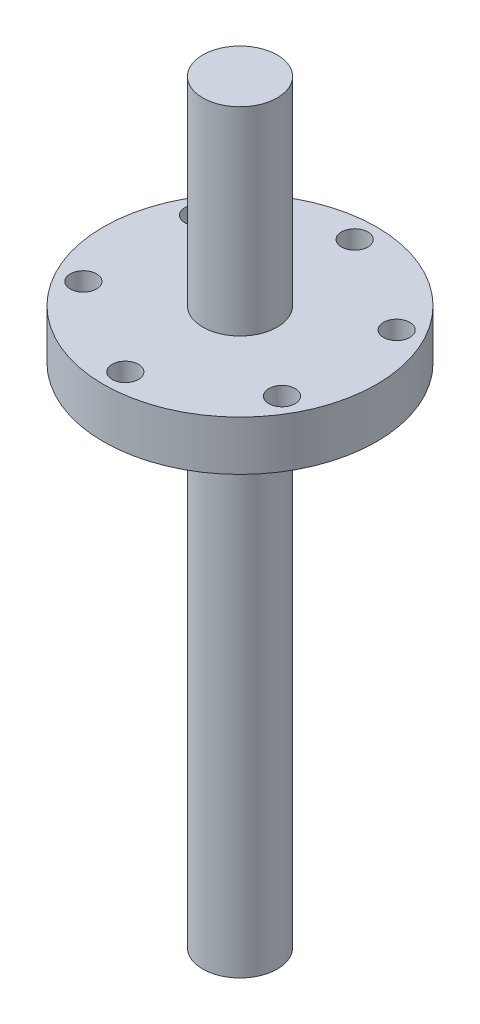
SolidWorks part; units mm, degrees
ref_plane "Front Plane" through (0, 0, 0) normal (0, 0, 1) x (1, 0, 0)
ref_plane "Top Plane" through (0, 0, 0) normal (0, 1, 0) x (1, 0, 0)
ref_plane "Right Plane" through (0, 0, 0) normal (1, 0, 0) x (0, 0, -1)
sketch "Sketch1" plane through (0, 0, 0) normal (0, 1, 0) x (1, 0, 0)
  circle A0 centre (0, 0) radius 34.925
  dimension "D1" = 69.85
extrude "Extrude1" add sketch "Sketch1" along normal blind 12.7
sketch "Sketch2" plane through (0, 0, 0) normal (0, 1, 0) x (1, 0, 0)
  circle A0 centre (0, 0) radius 17.399
  dimension "D1" = 34.798
extrude "Cut-Extrude1" [suppressed] cut sketch "Sketch2" along normal through all
sketch "Sketch3" plane through (0, 0, 0) normal (0, 1, 0) x (1, 0, 0)
  circle A0 centre (0, 29.337) radius 3.3655
  dimension "D1" = 6.731
  dimension "D2" = 29.337
extrude "Cut-Extrude2" cut sketch "Sketch3" along normal blind 12.7
ref_axis "Axis1" through (0, 35.8582, 0) along (0, -1, 0)
pattern_circular "CirPattern1" count 6 over 360 about axis through (0, 35.8582, 0) along (0, -1, 0) of "Cut-Extrude2"
sketch "Sketch4" plane through (0, 0, 0) normal (0, 1, 0) x (1, 0, 0)
  line L0 (0, 0) -> (0, 16.8619)
sketch "Sketch5" plane through (0, 0, 0) normal (0, 1, 0) x (1, 0, 0)
  circle A0 centre (0, 0) radius 9.525
  dimension "D1" = 19.05
extrude "Extrude2" add sketch "Sketch5" against normal blind 129.54
ref_plane "Plane1" through (0, 12.7, 0) normal (0, 1, 0) x (-1, 0, 0)
sketch "Sketch6" plane through (0, 12.7, 0) normal (0, 1, 0) x (-1, 0, 0)
  circle A0 centre (0, 0) radius 9.525
  dimension "D1" = 19.05
extrude "Extrude3" add sketch "Sketch6" along normal blind 50.8
